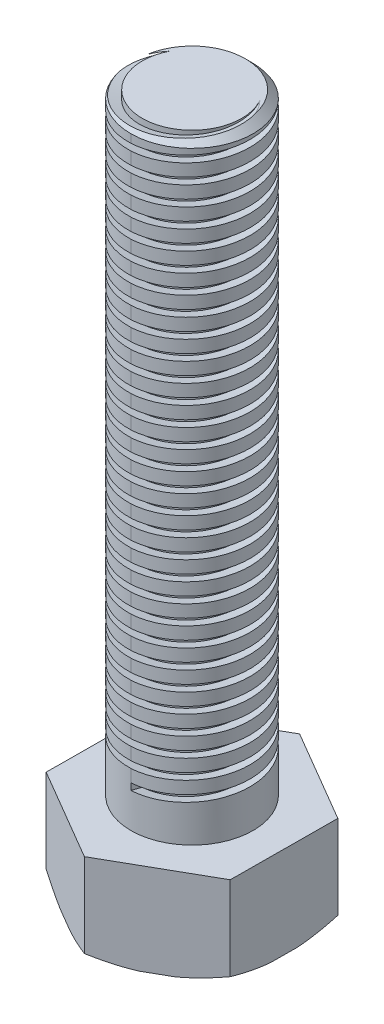
SolidWorks part; units mm, degrees
ref_plane "Front Plane" through (0, 0, 0) normal (0, 0, 1) x (1, 0, 0)
ref_plane "Top Plane" through (0, 0, 0) normal (0, 1, 0) x (1, 0, 0)
ref_plane "Right Plane" through (0, 0, 0) normal (1, 0, 0) x (0, 0, -1)
sketch "Sketch1" plane through (0, 0, 0) normal (0, 1, 0) x (1, 0, 0)
  line L1 (6.0399, -3.5385) -> (6.0844, 3.4615)
  line L2 (6.0844, 3.4615) -> (0.0445, 7)
  line L3 (0.0445, 7) -> (-6.0399, 3.5385)
  line L4 (-6.0399, 3.5385) -> (-6.0844, -3.4615)
  line L5 (-6.0844, -3.4615) -> (-0.0445, -7)
  line L6 (-0.0445, -7) -> (6.0399, -3.5385)
  circle A0 centre (0, 0) radius 6.0623 construction
  dimension "D1" = 14
extrude "Boss-Extrude1" add sketch "Sketch1" against normal blind 6
sketch "Sketch2" plane through (0, 0, 0) normal (0, 1, 0) x (1, 0, 0)
  circle A0 centre (0, 0) radius 4
  dimension "D1" = 8
extrude "Boss-Extrude2" add sketch "Sketch2" along normal blind 40
sketch "Sketch3" plane through (0, -6, 0) normal (0, -1, 0) x (1, 0, 0)
  circle A0 centre (0, 0) radius 6.1237
extrude "Cut-Extrude1" cut sketch "Sketch3" against normal blind 40 draft 60 flip side to cut
chamfer "Chamfer1" distance 0.5 angle 45 1 edges at (0, 40, 4)
sketch "Sketch4" plane through (0, 40, 0) normal (0, 1, 0) x (1, 0, 0)
  circle A0 centre (0, 0) radius 3.5
curve "Helix/Spiral1" pitch 1.25 height 37.5 radius 3.5 centre (0, 40, 0) axis (0, -1, 0) start towards (0, 0, 1)
sketch "Sketch5" plane through (0, 0, 0) normal (1, 0, 0) x (0, 0, -1)
  line L24 (-4, 40.2125) -> (-3.2557, 40.405)
  line L25 (-3.2557, 39.5825) -> (-3.2557, 40.405)
  line L26 (-3.2557, 39.5825) -> (-4, 39.775)
  line L27 (-4, 39.775) -> (-4, 40.2125)
  line L28 (-3.6279, 40.3088) -> (-3.6279, 39.6788) construction
  line L29 (-4, 39.9938) -> (-3.2557, 39.9938) construction
  point P8 (-3.6279, 39.9938)
  point P9 (-3.5, 40)
  point P10 (-7.0787, 40.7563)
  point P12 (-3.8988, 39.9938)
  point P13 (0, 0)
  dimension "D1" = 0.7443
  dimension "D2" = 0.63
  dimension "D3" = 29
  dimension "D4" = 0.5
sweep "Cut-Sweep3" cut profiles "Sketch5" path "Helix/Spiral1" align with end faces yes
